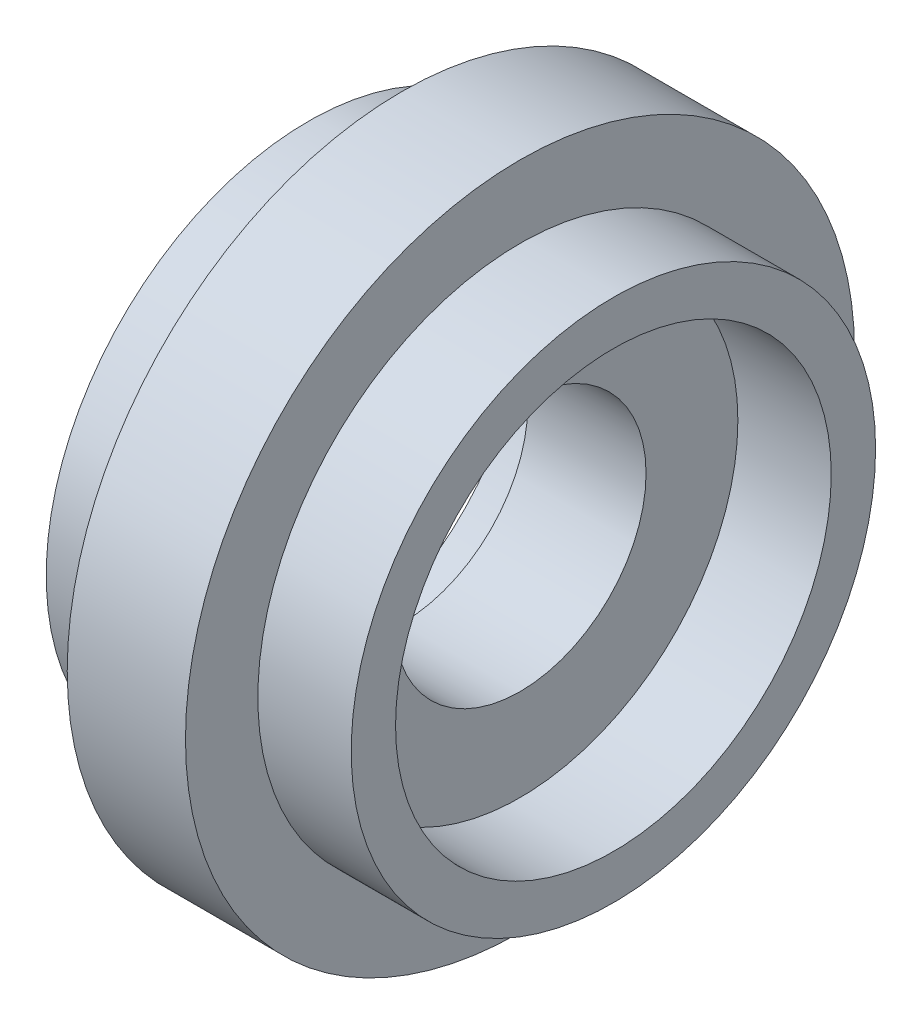
SolidWorks part; units mm, degrees
ref_plane "Ebene vorne" through (0, 0, 0) normal (0, 0, 1) x (1, 0, 0)
ref_plane "Ebene oben" through (0, 0, 0) normal (0, 1, 0) x (1, 0, 0)
ref_plane "Ebene rechts" through (0, 0, 0) normal (1, 0, 0) x (0, 0, -1)
sketch "Skizze1" plane through (0, 0, 0) normal (0, 0, 1) x (1, 0, 0)
  line L0 (0, 0) -> (-15579.6152, 0) construction
  line L1 (0, 0) -> (0, 10.75)
  line L2 (0, 10.75) -> (1.9, 10.75)
  line L3 (1.9, 10.75) -> (1.9, 8.425)
  line L4 (1.9, 8.425) -> (4.9, 8.425)
  line L5 (4.9, 8.425) -> (4.9, 7)
  line L6 (4.9, 7) -> (1.9, 7)
  line L7 (1.9, 7) -> (1.9, 0)
  line L8 (1.9, 0) -> (0, 0)
  dimension "D1" = 1.9
  dimension "D2" = 4.9
  dimension "D3" = 21.5
  dimension "D4" = 16.85
  dimension "D5" = 14
revolve "Rotation1" add sketch "Skizze1" angle 360 about L0
hole_wizard "Ø8.1 (8.1) Durchmesser Bohrung1" positions "Skizze2" profile "Skizze3" hole size "Ø8.1" standard "ISO" end condition through all
sketch "Skizze2" plane through (0, 0, 0) normal (-1, 0, 0) x (0, 0, 1)
  point P0 (0, 0)
sketch "Skizze3" plane through (0, 0, 0) normal (0, 1, 0) x (0, 0, 1)
  line L0 (0, 0) -> (0, 4.9)
  line L1 (0, 4.9) -> (4.05, 4.9)
  line L2 (4.05, 4.9) -> (4.05, 0)
  line L5 (4.05, 0) -> (0, 0)
  line L11 (0, -6.35) -> (0, 107.95) construction
  dimension "Bohrerdurchmesser" = 8.1
  dimension "Bohrungstiefe" = 4.9
mirror "Spiegeln1" about plane through (0, 0, 0) normal (1, 0, 0) of "Ø8.1 (8.1) Durchmesser Bohrung1", "Rotation1"
